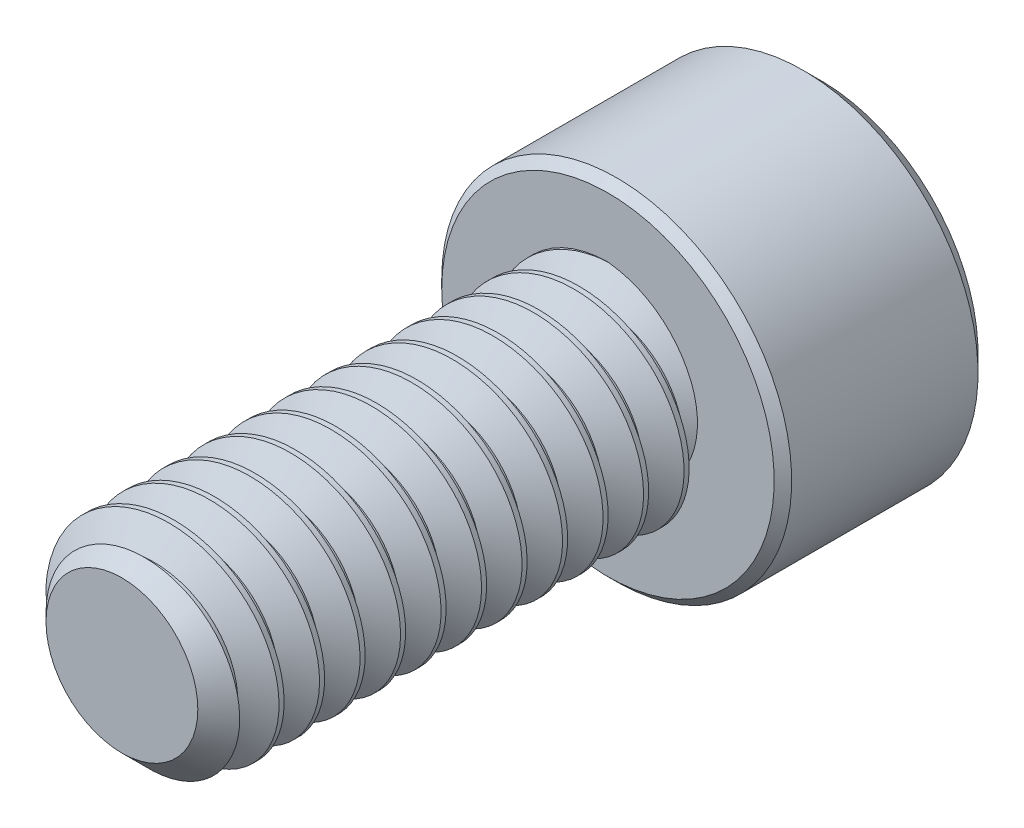
SolidWorks part; units mm, degrees
ref_plane "Front Plane" through (0, 0, 0) normal (0, 0, 1) x (1, 0, 0)
ref_plane "Top Plane" through (0, 0, 0) normal (0, 1, 0) x (1, 0, 0)
ref_plane "Right Plane" through (0, 0, 0) normal (1, 0, 0) x (0, 0, -1)
sketch "Sketch0" plane through (0, 0, 0) normal (1, 0, 0) x (0, 0, -1)
  line L0 (0, 0) -> (9.525, 0) construction
  point P2 (13.6906, 0)
  point P4 (0, 0)
  dimension "D1" = 9.525
  dimension "D2" = 4.1656
  dimension "Min Thread" = 0
sketch "Sketch1" plane through (0, 0, 0) normal (0, 0, 1) x (1, 0, 0)
  circle A0 centre (0, 0) radius 2.0828
  dimension "OD" = 4.1656
extrude "Extrude1" add sketch "Sketch1" against normal blind 9.525
sketch "Sketch2" plane through (0, 0, 0) normal (0, 0, 1) x (1, 0, 0)
  circle A0 centre (0, 0) radius 2.0828 construction
  circle A1 centre (0, 0) radius 2.0828
curve "Helix/Spiral1" pitch 0.7937 height 10.3188 turns 13 parameters "pitch"=0.7937
chamfer "Chamfer3" distance 0.5953 angle 45 1 edges at (2.0828, 0, 0)
sketch "Sketch3" plane through (0, 0, 0) normal (1, 0, 0) x (0, 0, -1)
  line L0 (-0.6945, 2.0828) -> (-0.3969, 1.5672)
  line L1 (-0.3969, 1.5672) -> (-0.2977, 1.5672)
  line L2 (-0.2977, 1.5672) -> (0, 2.0828)
  line L3 (-0.6945, 2.0828) -> (0, 2.0828)
  line L4 (-0.3473, 2.0828) -> (-0.3473, 1.5672) construction
  line L5 (-0.5457, 1.825) -> (-0.1488, 1.825) construction
  line L6 (0, 2.0828) -> (0, -2.0828) construction
  dimension "D1" = 0.0992
  dimension "D2" = 0.3969
  dimension "D3" = 60
sweep "Cut-Sweep1" cut profiles "Sketch3" path "Helix/Spiral1"
sketch "Sketch5" plane through (0, 0, 0) normal (1, 0, 0) x (0, 0, -1)
  line L0 (9.525, -1.5805) -> (9.525, 1.4861) construction
  line L1 (9.525, 2.0828) -> (0, 2.0828)
  line L2 (9.525, 2.0828) -> (9.525, 0)
  line L3 (9.525, 0) -> (-0.7581, 0)
  line L4 (0, 0) -> (9.525, 0) construction
  line L5 (0, 2.0828) -> (-0.7581, 0)
  line L6 (0, 0) -> (12.065, 0) construction
  dimension "D1" = 70
  dimension "D3" = 2.54
revolve "partially thread" [suppressed] add sketch "Sketch5" angle 360 about L6
sketch "Sketch6" plane through (0, 0, -9.525) normal (0, 0, -1) x (-1, 0, 0)
  circle A0 centre (0, 0) radius 3.429
  dimension "head dia" = 6.858
extrude "Extrude2" add sketch "Sketch6" along normal blind 4.1656
sketch "Sketch7" plane through (0, 0, -13.6906) normal (0, 0, -1) x (-1, 0, 0)
  line L1 (0, 2.0622) -> (-1.7859, 1.0311)
  line L2 (-1.7859, 1.0311) -> (-1.7859, -1.0311)
  line L3 (-1.7859, -1.0311) -> (0, -2.0622)
  line L4 (0, -2.0622) -> (1.7859, -1.0311)
  line L5 (1.7859, -1.0311) -> (1.7859, 1.0311)
  line L6 (1.7859, 1.0311) -> (0, 2.0622)
  circle A0 centre (0, 0) radius 1.7859 construction
  dimension "hex dia" = 3.5719
extrude "Cut-Extrude1" cut sketch "Sketch7" against normal blind 2.6789
sketch "Sketch8" plane through (0, 0, -13.6906) normal (0, 0, -1) x (-1, 0, 0)
  circle A0 centre (0, 0) radius 2.0622
extrude "Cut-Extrude2" cut sketch "Sketch8" against normal through all draft 45
chamfer "Chamfer1" distance 0.3429 angle 45 1 edges at (-3.429, 0, -13.6906)
chamfer "Chamfer2" distance 0.1715 angle 45 1 edges at (-3.429, 0, -9.525)
sketch "Sketch9" plane through (0, 0, 0) normal (1, 0, 0) x (0, 0, -1)
  line L0 (0, 2.0828) -> (0, -2.0828) construction
  line L1 (1.9844, 2.0828) -> (1.9844, -2.0828) construction
  line L2 (13.6906, 3.429) -> (13.6906, -3.429) construction
  line L3 (9.525, 3.429) -> (9.525, -3.429) construction
  line L4 (9.525, 3.2575) -> (9.525, -3.2575) construction
  line L5 (13.6906, -3.0861) -> (13.6906, 3.0861) construction
  line L6 (9.525, -3.429) -> (9.525, 3.429) construction
  line L7 (0, 1.4875) -> (0, -1.4875) construction
  line L8 (-0.6945, 2.0828) -> (0, 2.0828) construction
  line L9 (1.9844, 0) -> (0, 0) construction
  dimension "D1" = 1.9844
equation "\"D3@Helix/Spiral1\" = \"screw length@Extrude1\"+\"pitch@Helix/Spiral1\""
equation "\"D1@Sketch3\" = \"pitch@Helix/Spiral1\"*.125"
equation "\"D2@Sketch3\" = \"pitch@Helix/Spiral1\"*.5"
equation "\"D1@Cut-Extrude1\" = \"hex dia@Sketch7\"*.75"
equation "\"D1@Chamfer1\" = \"head dia@Sketch6\"*.05"
equation "\"D1@Sketch9\" = \"pitch@Helix/Spiral1\"*2.50"
equation "\"D1@Chamfer2\" = \"D1@Chamfer1\"/2"
equation "\"D1@Chamfer3\" = \"pitch@Helix/Spiral1\"*.750"
equation "\"D1@Sketch0\" = \"screw length@Extrude1\""
equation "\"D2@Sketch0\" = \"head depth@Extrude2\""
